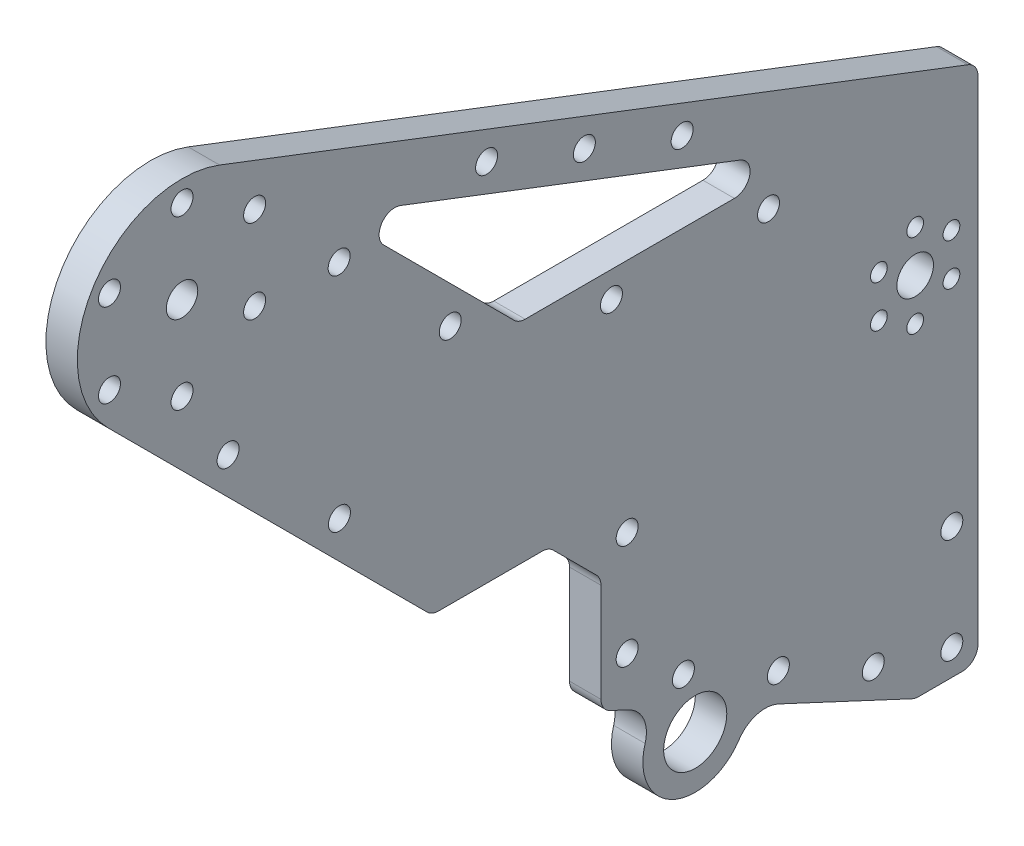
SolidWorks part; units mm, degrees
material "Thornel Mat VMA"
ref_plane "前视基准面" through (0, 0, 0) normal (0, 0, 1) x (1, 0, 0)
ref_plane "上视基准面" through (0, 0, 0) normal (0, 1, 0) x (1, 0, 0)
ref_plane "右视基准面" through (0, 0, 0) normal (1, 0, 0) x (0, 0, -1)
other "Configuration Table"
sketch "草图1" plane through (0, 0, 0) normal (1, 0, 0) x (0, 0, -1)
  line L0 (0, 0) -> (0, -70) construction
  line L1 (0, -70) -> (-120, -14.0431)
  line L2 (0, -70) -> (43.7623, -70) construction
  line L3 (-38.9711, 5.625) -> (-49.0211, 5.625) construction
  line L4 (-60, -42.0215) -> (-60, -14.9465) construction
  line L5 (-73.7711, 0.625) -> (-24.2711, 0.625) construction
  line L6 (-73.7711, 0.625) -> (-73.7711, 10.625) construction
  line L7 (-73.7711, 10.625) -> (-24.2711, 10.625) construction
  line L8 (-24.2711, 0.625) -> (-24.2711, 10.625) construction
  line L9 (-73.7711, 0.625) -> (-24.2711, 10.625) construction
  line L10 (-73.7711, 10.625) -> (-24.2711, 0.625) construction
  line L11 (-38.9711, -16.875) -> (0, -16.875) construction
  line L12 (12, -70) -> (12, 30)
  line L13 (-28.7711, -4.625) -> (-69.2711, -4.625) construction
  line L14 (-28.7711, -4.625) -> (-28.7711, 15.875) construction
  line L15 (-28.7711, 15.875) -> (-69.2711, 15.875) construction
  line L16 (-69.2711, -4.625) -> (-69.2711, 15.875) construction
  line L17 (-28.7711, -4.625) -> (-69.2711, 15.875) construction
  line L18 (-28.7711, 15.875) -> (-69.2711, -4.625) construction
  line L19 (0, -70) -> (12, -70)
  line L20 (-120, -10) -> (-120, -14.0431)
  line L21 (-120, 30) -> (12, 30)
  line L22 (0, -70) -> (-23.662, -70)
  line L23 (-23.662, -70) -> (-120, -25.0769)
  line L24 (-120, -25.0769) -> (-120, -14.0431)
  line L25 (-120, -10) -> (-60, -10)
  line L26 (-60, -10) -> (-60, -42.0215)
  line L27 (-70, -10) -> (-70, -37.3585)
  line L28 (-125.8579, 80.1421) -> (-75.7157, 30)
  line L29 (-154.1421, 51.8579) -> (-92.2843, -10)
  line L31 (1.395, 2.5273) -> (-1.4912, 2.4717) construction
  line L32 (-1.4912, 2.4717) -> (-2.8862, -0.0556) construction
  line L33 (-2.8862, -0.0556) -> (-1.395, -2.5273) construction
  line L34 (-1.395, -2.5273) -> (1.4912, -2.4717) construction
  line L35 (1.4912, -2.4717) -> (2.8862, 0.0556) construction
  line L36 (2.8862, 0.0556) -> (1.395, 2.5273) construction
  circle A0 centre (0, 0) radius 50.8 construction
  circle A1 centre (0, 0) radius 16.875 construction
  circle A2 centre (-38.9711, 5.625) radius 22.5 construction
  circle A3 centre (-120, 10) radius 20 construction
  circle A4 centre (-120, 10) radius 3
  circle A5 centre (0, 0) radius 3.5
  circle A6 centre (-73.7711, 10.625) radius 2.1 construction
  circle A7 centre (-73.7711, 0.625) radius 2.1 construction
  circle A8 centre (-24.2711, 10.625) radius 2.1 construction
  circle A9 centre (-24.2711, 0.625) radius 2.1 construction
  circle A10 centre (-140, 66) radius 20
  circle A11 centre (-38.9711, 5.625) radius 4 construction
  circle A12 centre (0, 0) radius 2.5 construction
  dimension "D1" = 101.6
  dimension "D2" = 33.75
  dimension "D3" = 45
  dimension "D6" = 40
  dimension "D7" = 6
  dimension "D9" = 7
  dimension "D13" = 4.2
  dimension "D17" = 120
  dimension "D18" = 10
  dimension "D21" = 40
  dimension "D22" = 70
  dimension "D23" = 136
  dimension "D25" = 8
  dimension "D26" = 5
  dimension "D4" = 65
  dimension "D5" = 70
  dimension "D8" = 60
  dimension "D10" = 10.05
  dimension "D11" = 10
  dimension "D12" = 49.5
  dimension "D14" = 20.5
  dimension "D15" = 40.5
  dimension "D16" = 12
  dimension "D19" = 10
  dimension "D20" = 10
  dimension "D24" = 135
extrude "凸台-拉伸1" add sketch "草图1" along normal mid plane 6 contours A3 A4 | A3 L25 L26 L1 L19 L12 L21 A9 A8 A7 A6 A5 L13 L16 L15 L14 | A10 region at (0, -0.4977, 48.9373) region at (0, 66, 140)
sketch "草图2" plane through (3, 0, 0) normal (1, 0, 0) x (0, 0, -1)
  line L0 (-140, 82) -> (-140, 66) construction
  circle A0 centre (-140, 66) radius 3
  circle A1 centre (-140, 82) radius 2.1
  circle A2 centre (-126.1436, 74) radius 2.1
  circle A3 centre (-126.1436, 58) radius 2.1
  circle A4 centre (-140, 50) radius 2.1
  circle A5 centre (-153.8564, 58) radius 2.1
  circle A6 centre (-153.8564, 74) radius 2.1
  point P17 (-140, 66)
  dimension "D1" = 6
  dimension "D2" = 4.2
  dimension "D3" = 16
  dimension "D4" = 6
extrude "切除-拉伸1" cut sketch "草图2" against normal blind 10
sketch "草图3" plane through (3, 0, 0) normal (1, 0, 0) x (0, 0, -1)
  circle A6 centre (0, 0) radius 8 construction
  circle A7 centre (0, 8) radius 1.6
  circle A8 centre (6.9282, 4) radius 1.6
  circle A9 centre (6.9282, -4) radius 1.6
  circle A10 centre (0, -8) radius 1.6
  circle A11 centre (-6.9282, -4) radius 1.6
  circle A12 centre (-6.9282, 4) radius 1.6
  point P18 (0, 0)
  dimension "D1" = 6
  dimension "D2" = 3.2
  dimension "D4" = 16
sketch "草图4" plane through (3, 0, 0) normal (1, 0, 0) x (0, 0, -1)
  line L0 (-60, -10) -> (-60, -42.0215) construction
  line L1 (-92.2843, -10) -> (-60, -10) construction
  line L2 (12, -70) -> (12, 30) construction
  line L4 (0, -70) -> (12, -70) construction
  line L5 (0, -70) -> (-60, -42.0215) construction
  circle A0 centre (-55, -15) radius 2.1
  circle A1 centre (-55, -35) radius 2.1
  circle A2 centre (7, -65) radius 2.1
  circle A3 centre (7, -45) radius 2.1
  circle A4 centre (-8, -60.7526) radius 2.1
  circle A5 centre (-26.1262, -52.3003) radius 2.1
  circle A6 centre (-44.2523, -43.8479) radius 2.1
  dimension "D1" = 4.2
  dimension "D2" = 5
  dimension "D3" = 5
  dimension "D5" = 4.2
  dimension "D6" = 5
  dimension "D7" = 5
  dimension "D9" = 4.2
  dimension "D10" = 5
  dimension "D11" = 20
  dimension "D4" = 2
  dimension "D8" = 2
  dimension "D12" = 3
extrude "切除-拉伸3" cut sketch "草图4" against normal blind 10
chamfer "倒角1" distance 10 angle 45 1 edges at (0, -10, 60)
fillet "圆角1" radius 3 8 edges at (0, 30, -12) (0, -70, -12) (0, -70, 0) (0, -42.0215, 60) (0, -20, 60) (0, -10, 70) (0, 30, 75.7157) (0, -10, 92.2843)
sketch "草图5" plane through (3, 0, 0) normal (1, 0, 0) x (0, 0, -1)
  line L0 (-110, 57.2132) -> (-88.7868, 36) construction
  line L1 (-125.8579, 80.1421) -> (-76.5944, 30.8787) construction
  line L2 (-95.4046, 49.6888) -> (-123.6525, 21.3683) construction
  line L3 (-154.1421, 51.8579) -> (-93.163, -9.1213) construction
  line L4 (-109.5286, 35.5286) -> (-99.6927, 25.7179) construction
  line L5 (-131.2143, 35.9443) -> (-109.9468, 14.7857) construction
  line L6 (-75.6211, 30.2284) -> (-74.4731, 33) construction
  line L7 (-58, 25) -> (-28, 25) construction
  line L9 (-74.4731, 30) -> (9, 30) construction
  line L10 (12, -67) -> (12, 27) construction
  circle A0 centre (-110, 57.2132) radius 2.1
  circle A1 centre (-88.7868, 36) radius 2.1
  circle A2 centre (-140, 66) radius 3 construction
  circle A3 centre (-109.9468, 14.7857) radius 2.1
  circle A4 centre (-131.2143, 35.9443) radius 2.1
  arc A5 (-76.5944, 30.8787) -> (-74.4731, 30) centre (-74.4731, 33) ccw construction
  circle A6 centre (-58, 25) radius 2.1
  circle A7 centre (-28, 25) radius 2.1
  dimension "D1" = 4.2
  dimension "D3" = 30
  dimension "D6" = 4.2
  dimension "D7" = 4.2
  dimension "D8" = 5
  dimension "D9" = 40
  dimension "D2" = 30
  dimension "D4" = 5
  dimension "D5" = 30
extrude "切除-拉伸4" cut sketch "草图5" against normal blind 10
extrude "切除-拉伸5" cut sketch "草图3" against normal blind 10
sketch "草图6" plane through (3, 0, 0) normal (1, 0, 0) x (0, 0, -1)
  line L0 (-42, -72) -> (5.2941, -72) construction
  line L1 (0.6651, -70) -> (9, -70) construction
  line L3 (-39.1132, -54.5) -> (-40.5566, -52) construction
  line L4 (-40.5566, -52) -> (-43.4434, -52) construction
  line L5 (-43.4434, -52) -> (-44.8868, -54.5) construction
  line L6 (-44.8868, -54.5) -> (-43.4434, -57) construction
  line L7 (-43.4434, -57) -> (-40.5566, -57) construction
  line L8 (-40.5566, -57) -> (-39.1132, -54.5) construction
  line L9 (12, -67) -> (12, 27) construction
  line L10 (-32.9369, -58.7262) -> (-31.3723, -55.3709)
  line L11 (-0.6028, -69.7189) -> (-58.2679, -42.8293) construction
  line L12 (-51.0631, -50.2738) -> (-49.4985, -46.9185)
  line L13 (-49.4985, -46.9185) -> (-31.3723, -55.3709)
  circle A0 centre (-42, -54.5) radius 17.5 construction
  circle A1 centre (-42, -54.5) radius 6.025
  circle A2 centre (-42, -54.5) radius 2.5 construction
  circle A3 centre (-42, -54.5) radius 3.5 construction
  circle A4 centre (-42, -54.5) radius 10
  line M46 (-58.2679, -42.8293) -> (-0.6028, -69.7189)
  dimension "D1" = 2
  dimension "D2" = 35
  dimension "D3" = 12.05
  dimension "D4" = 5
  dimension "D5" = 7
  dimension "D6" = 54
  dimension "D7" = 20
extrude "凸台-拉伸2" add sketch "草图6" against normal up to surface (6 mm away) contours L13 A4 A1 M46 | A4 L12 M46 | A4 L10 L13 region at (3, -56.1141, 31.9526) region at (3, -63.3236, 46.1145) region at (3, -47.8408, 49.6948) up to face at (-3, -4, 5.3282)
extrude "切除-拉伸6" cut sketch "草图6<3>" against normal through all both contours L13 A1 region at (3, -50.2869, 40.0354)
sketch "草图6<3>" plane through (3, 0, 0) normal (1, 0, 0) x (0, 0, -1) same geometry as "草图6"
fillet "圆角2" radius 6 2 edges at (0, -46.9185, 49.4985) (0, -55.3709, 31.3723)
sketch "草图7" plane through (3, 0, 0) normal (1, 0, 0) x (0, 0, -1)
  line L0 (-132.8311, 84.671) -> (10.0753, 29.8007)
  line L1 (-136.4155, 75.3355) -> (6.4909, 20.4651)
  line L2 (-61.3779, 57.2358) -> (-64.9623, 47.9003) construction
  line L10 (-26.0848, -57.8365) -> (-0.6028, -69.7189)
  line L11 (0.6651, -70) -> (9, -70)
  line L12 (12, -67) -> (12, 27)
  line L13 (9, 30) -> (-74.4731, 30)
  line L14 (-76.5944, 30.8787) -> (-125.8579, 80.1421)
  line L15 (-154.1421, 51.8579) -> (-93.163, -9.1213)
  line L16 (-91.0416, -10) -> (-71.2426, -10)
  line L17 (-69.1213, -10.8787) -> (-60.8787, -19.1213)
  line L18 (-60, -21.2426) -> (-60, -40.1103)
  line L19 (-58.2679, -42.8293) -> (-54.786, -44.4529)
  line L20 (-26.0848, -57.8365) -> (-0.6028, -69.7189)
  line L21 (0.6651, -70) -> (9, -70)
  line L22 (12, -67) -> (12, 27)
  line L23 (9, 30) -> (-74.4731, 30)
  line L24 (-76.5944, 30.8787) -> (-125.8579, 80.1421)
  line L25 (-154.1421, 51.8579) -> (-93.163, -9.1213)
  line L26 (-91.0416, -10) -> (-71.2426, -10)
  line L27 (-69.1213, -10.8787) -> (-60.8787, -19.1213)
  line L28 (-60, -21.2426) -> (-60, -40.1103)
  line L29 (-58.2679, -42.8293) -> (-54.786, -44.4529)
  circle A0 centre (-63.1701, 52.5681) radius 2.1
  circle A1 centre (-44.4991, 45.3992) radius 2.1
  circle A2 centre (-81.8411, 59.737) radius 2.1
  arc A12 (-51.5761, -51.6192) -> (-33.6378, -59.9839) centre (-42, -54.5) ccw
  arc A13 (-26.0848, -57.8365) -> (-33.6378, -59.9839) centre (-28.6205, -63.2743) ccw
  arc A14 (-0.6028, -69.7189) -> (0.6651, -70) centre (0.6651, -67) ccw
  arc A15 (9, -70) -> (12, -67) centre (9, -67) ccw
  arc A16 (12, 27) -> (9, 30) centre (9, 27) ccw
  arc A17 (-76.5944, 30.8787) -> (-74.4731, 30) centre (-74.4731, 33) ccw
  arc A18 (-125.8579, 80.1421) -> (-154.1421, 51.8579) centre (-140, 66) ccw
  arc A19 (-93.163, -9.1213) -> (-91.0416, -10) centre (-91.0416, -7) ccw
  arc A20 (-69.1213, -10.8787) -> (-71.2426, -10) centre (-71.2426, -13) ccw
  arc A21 (-60, -21.2426) -> (-60.8787, -19.1213) centre (-63, -21.2426) ccw
  arc A22 (-60, -40.1103) -> (-58.2679, -42.8293) centre (-57, -40.1103) ccw
  arc A23 (-51.5761, -51.6192) -> (-54.786, -44.4529) centre (-57.3217, -49.8907) ccw
  arc A24 (-51.5761, -51.6192) -> (-33.6378, -59.9839) centre (-42, -54.5) ccw
  arc A25 (-26.0848, -57.8365) -> (-33.6378, -59.9839) centre (-28.6205, -63.2743) ccw
  arc A26 (-0.6028, -69.7189) -> (0.6651, -70) centre (0.6651, -67) ccw
  arc A27 (9, -70) -> (12, -67) centre (9, -67) ccw
  arc A28 (12, 27) -> (9, 30) centre (9, 27) ccw
  arc A29 (-76.5944, 30.8787) -> (-74.4731, 30) centre (-74.4731, 33) ccw
  arc A30 (-125.8579, 80.1421) -> (-154.1421, 51.8579) centre (-140, 66) ccw
  arc A31 (-93.163, -9.1213) -> (-91.0416, -10) centre (-91.0416, -7) ccw
  arc A32 (-69.1213, -10.8787) -> (-71.2426, -10) centre (-71.2426, -13) ccw
  arc A33 (-60, -21.2426) -> (-60.8787, -19.1213) centre (-63, -21.2426) ccw
  arc A34 (-60, -40.1103) -> (-58.2679, -42.8293) centre (-57, -40.1103) ccw
  arc A35 (-51.5761, -51.6192) -> (-54.786, -44.4529) centre (-57.3217, -49.8907) ccw
  arc M35 (12, 27) -> (9, 30) centre (9, 27) ccw
  line M36 (9, 30) -> (-74.4731, 30)
  line M38 (-76.5944, 30.8787) -> (-125.8579, 80.1421)
  arc M39 (-125.8579, 80.1421) -> (-154.1421, 51.8579) centre (-140, 66) ccw
  dimension "D3" = 4.2
  dimension "D2" = 10
  dimension "D1" = 0
  dimension "D4" = 2
extrude "凸台-拉伸3" add sketch "草图7" against normal up to surface (6 mm away) contours L2 L0 L1 A0 A2 M39 M38 | L0 L2 A0 L1 A1 M36 M35 region at (3, 64.1878, 92.5218) region at (3, 41.2317, 32.6503) up to face at (-3, -54.5, 35.975)
fillet "圆角3" radius 3 2 edges at (0, 30, 18.3421) (0, 65.7594, 111.4751)
